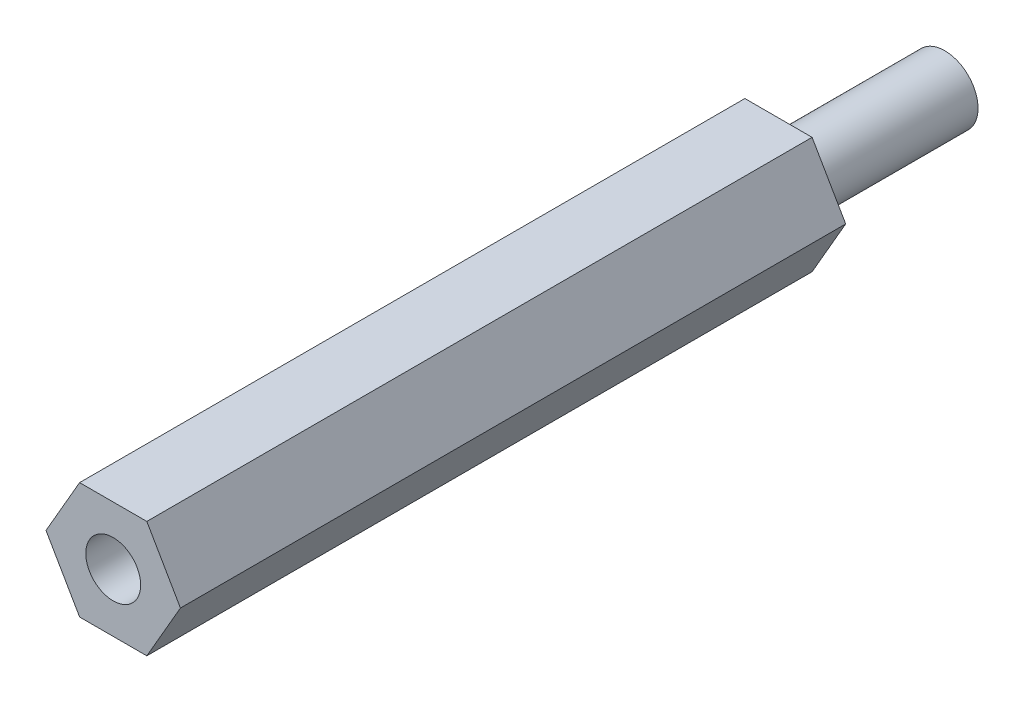
SolidWorks part; units mm, degrees
material "黃銅"
ref_plane "前基準面" through (0, 0, 0) normal (0, 0, 1) x (1, 0, 0)
ref_plane "上基準面" through (0, 0, 0) normal (0, 1, 0) x (1, 0, 0)
ref_plane "右基準面" through (0, 0, 0) normal (1, 0, 0) x (0, 0, -1)
sketch "草圖1" plane through (0, 0, 0) normal (0, 0, 1) x (1, 0, 0)
  line L1 (-2.0207, 3.5) -> (-4.0415, 0)
  line L2 (-4.0415, 0) -> (-2.0207, -3.5)
  line L3 (-2.0207, -3.5) -> (2.0207, -3.5)
  line L4 (2.0207, -3.5) -> (4.0415, 0)
  line L5 (4.0415, 0) -> (2.0207, 3.5)
  line L6 (2.0207, 3.5) -> (-2.0207, 3.5)
  circle A0 centre (0, 0) radius 3.5 construction
  dimension "D1" = 7
extrude "填料-伸長1" add sketch "草圖1" along normal blind 40
sketch "草圖4" plane through (0, 0, 0) normal (0, 0, -1) x (-1, 0, 0)
  circle A0 centre (0, 0) radius 2
  dimension "D1" = 4
extrude "填料-伸長2" add sketch "草圖4" along normal blind 10
hole_wizard "M4x0.7 螺紋孔1" positions "草圖2" profile "草圖3" tap size "M4x0.7" standard "Ansi Metric"
sketch "草圖2" plane through (0, 0, 40) normal (0, 0, 1) x (1, 0, 0)
  point P0 (0, 0)
sketch "草圖3" plane through (0, 0, 40) normal (1, 0, 0) x (0, -1, 0)
  line L0 (0, 0) -> (0, 11.0914)
  line L1 (0, 11.0914) -> (1.65, 10.1)
  line L2 (1.65, 10.1) -> (1.65, 0)
  line L5 (1.65, 0) -> (0, 0)
  line L10 (0, 11.0914) -> (-1.65, 10.1) construction
  line L11 (0, -6.35) -> (0, 107.95) construction
  dimension "螺孔鑽直徑" = 3.3
  dimension "螺孔鑽深度" = 10.1
  dimension "導頭角度" = 118
